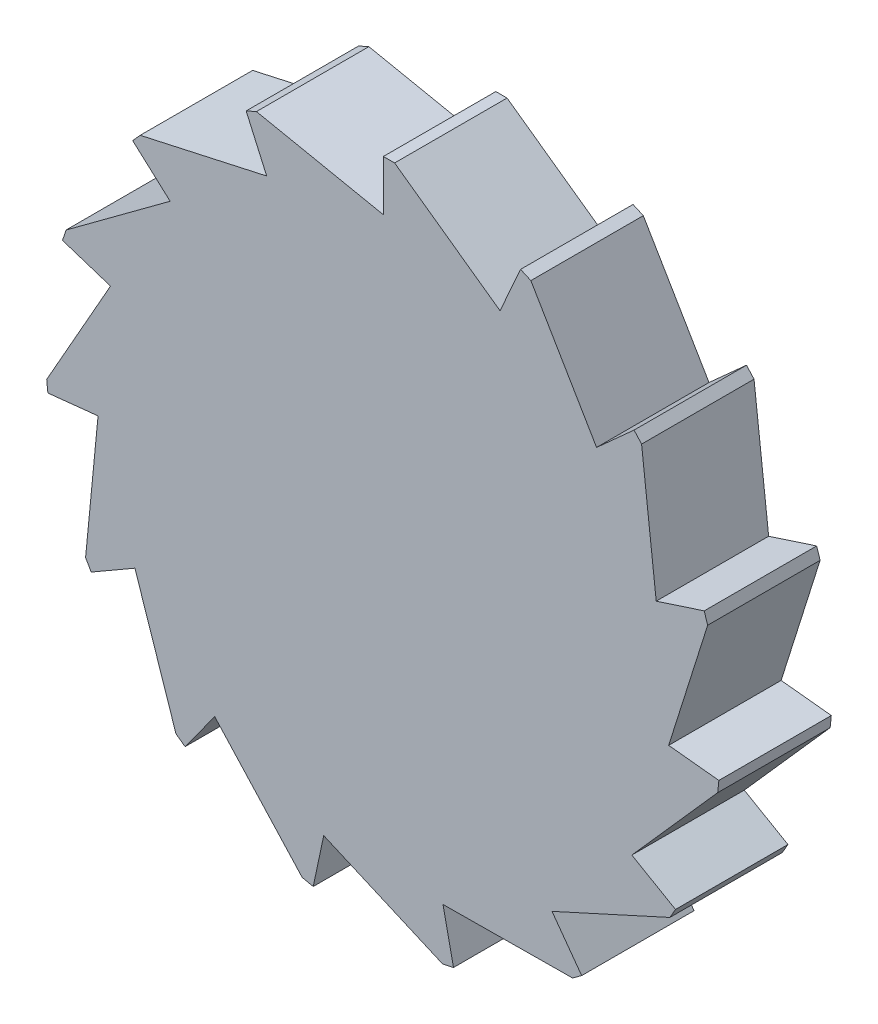
SolidWorks part; units mm, degrees
ref_plane "Front Plane" through (0, 0, 0) normal (0, 0, 1) x (1, 0, 0)
ref_plane "Top Plane" through (0, 0, 0) normal (0, 1, 0) x (1, 0, 0)
ref_plane "Right Plane" through (0, 0, 0) normal (1, 0, 0) x (0, 0, -1)
sketch "Sketch1" plane through (0, 0, 0) normal (0, 0, 1) x (1, 0, 0)
  line L0 (0, 25.5126) -> (0, 30)
  line L1 (0, 30) -> (1.0009, 30)
  line L2 (1.0009, 30) -> (10.3769, 23.307)
  line L3 (13.1165, 26.9993) -> (18.9596, 17.0713)
  line L4 (10.3769, 23.307) -> (12.2021, 27.4064)
  line L5 (12.2021, 27.4064) -> (13.1165, 26.9993)
  line L6 (22.9641, 19.3301) -> (24.264, 7.8838)
  line L7 (18.9596, 17.0713) -> (22.2943, 20.0739)
  line L8 (22.2943, 20.0739) -> (22.9641, 19.3301)
  line L9 (28.841, 8.3186) -> (25.3729, -2.6668)
  line L10 (24.264, 7.8838) -> (28.5317, 9.2705)
  line L11 (28.5317, 9.2705) -> (28.841, 8.3186)
  line L12 (29.731, -4.1313) -> (22.0946, -12.7563)
  line L13 (25.3729, -2.6668) -> (29.8357, -3.1359)
  line L14 (29.8357, -3.1359) -> (29.731, -4.1313)
  line L15 (25.4803, -15.8668) -> (14.996, -20.6402)
  line L16 (22.0946, -12.7563) -> (25.9808, -15)
  line L17 (25.9808, -15) -> (25.4803, -15.8668)
  line L18 (16.8238, -24.8588) -> (5.3044, -24.9551)
  line L19 (14.996, -20.6402) -> (17.6336, -24.2705)
  line L20 (17.6336, -24.2705) -> (16.8238, -24.8588)
  line L21 (5.2583, -29.5525) -> (-5.3044, -24.9551)
  line L22 (5.3044, -24.9551) -> (6.2374, -29.3444)
  line L23 (6.2374, -29.3444) -> (5.2583, -29.5525)
  line L24 (-7.2164, -29.1363) -> (-14.996, -20.6402)
  line L25 (-5.3044, -24.9551) -> (-6.2374, -29.3444)
  line L26 (-6.2374, -29.3444) -> (-7.2164, -29.1363)
  line L27 (-18.4433, -23.6822) -> (-22.0946, -12.7563)
  line L28 (-14.996, -20.6402) -> (-17.6336, -24.2705)
  line L29 (-17.6336, -24.2705) -> (-18.4433, -23.6822)
  line L30 (-26.4812, -14.1332) -> (-25.3729, -2.6668)
  line L31 (-22.0946, -12.7563) -> (-25.9808, -15)
  line L32 (-25.9808, -15) -> (-26.4812, -14.1332)
  line L33 (-29.9403, -2.1404) -> (-24.264, 7.8838)
  line L34 (-25.3729, -2.6668) -> (-29.8357, -3.1359)
  line L35 (-29.8357, -3.1359) -> (-29.9403, -2.1404)
  line L36 (-28.2224, 10.2224) -> (-18.9596, 17.0713)
  line L37 (-24.264, 7.8838) -> (-28.5317, 9.2705)
  line L38 (-28.5317, 9.2705) -> (-28.2224, 10.2224)
  line L39 (-21.6246, 20.8177) -> (-10.3769, 23.307)
  line L40 (-18.9596, 17.0713) -> (-22.2943, 20.0739)
  line L41 (-22.2943, 20.0739) -> (-21.6246, 20.8177)
  line L42 (-11.2877, 27.8135) -> (0, 25.5126)
  line L43 (-10.3769, 23.307) -> (-12.2021, 27.4064)
  line L44 (-12.2021, 27.4064) -> (-11.2877, 27.8135)
  line L45 (0, 0) -> (14.3091, 20.5) construction
  circle A0 centre (0, 0) radius 25 construction
  circle A1 centre (0, 0) radius 4
  dimension "D1" = 50
  dimension "D8" = 8
  dimension "D2" = 4.4874
  dimension "D3" = 1.0009
  dimension "D4" = 25.5126
  dimension "D6" = 25
  dimension "D7" = 10.3769
  dimension "D5" = 15
extrude "Boss-Extrude1" add sketch "Sketch1" along normal blind 10 contours L30 L34 L35 L33 L37 L38 L36 L40 L41 L39 L43 L44 L42 L0 L1 L2 L4 L5 L3 L7 L8 L6 L10 L11 L9 L13 L14 L12 L16 L17 L15 L19 L20 L18 L22 L23 L21 L25 L26 L24 L28 L29 L27 L31 L32
